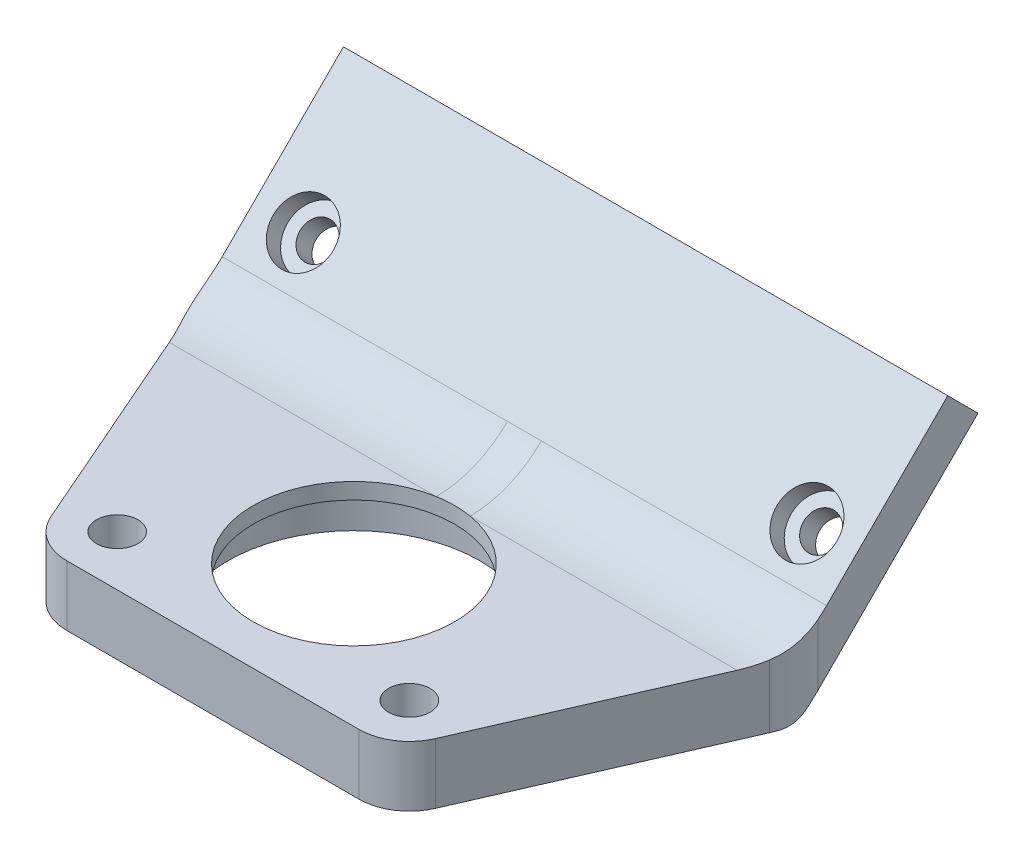
SolidWorks part; units mm, degrees
ref_plane "Alzado" through (0, 0, 0) normal (0, 0, 1) x (1, 0, 0)
ref_plane "Planta" through (0, 0, 0) normal (0, 1, 0) x (1, 0, 0)
ref_plane "Vista lateral" through (0, 0, 0) normal (1, 0, 0) x (0, 0, -1)
sketch "Croquis2" plane through (0, 0, 0) normal (1, 0, 0) x (0, 0, -1)
  line L0 (0, 0) -> (-28, 0)
  line L1 (-28, 0) -> (-28, 6)
  line L2 (-28, 6) -> (0, 6)
  line L3 (0, 6) -> (14.9605, 20.9605)
  line L4 (14.9605, 20.9605) -> (17.9605, 17.9605)
  line L5 (17.9605, 17.9605) -> (0, 0)
  dimension "D1" = 6
  dimension "D2" = 28
  dimension "D3" = 28
  dimension "D4" = 25.4
  dimension "D5" = 45
extrude "Saliente-Extruir1" add sketch "Croquis2" along normal blind 30 and the other way blind 30
ref_plane "Plano1" through (0, 0, 0) normal (0, -0.7071, -0.7071) x (-1, 0, 0)
sketch "Croquis3" plane through (0, 0, 0) normal (0, -0.7071, -0.7071) x (-1, 0, 0)
  line L0 (0, 0) -> (0, 25.4) construction
  line L1 (30, 25.4) -> (-30, 25.4) construction
  line L2 (-25, 12.7) -> (25, 12.7) construction
  circle A0 centre (-25, 12.7) radius 1.75
  circle A1 centre (25, 12.7) radius 1.75
  point P8 (0, 12.7)
  dimension "D2" = 3.5
  dimension "D1" = 50
extrude "Cortar-Extruir1" cut sketch "Croquis3" against normal up to surface (4.2426 mm away) up to face at (0, 13.4803, -7.4803)
ref_plane "Plano2" through (0, 3, 3) normal (0, 0.7071, 0.7071) x (1, 0, 0)
sketch "Croquis4" plane through (0, 3, 3) normal (0, 0.7071, 0.7071) x (1, 0, 0)
  circle A0 centre (-25, 12.7) radius 3
  circle A1 centre (25, 12.7) radius 3
  dimension "D1" = 6
extrude "Cortar-Extruir2" cut sketch "Croquis4" against normal blind 2
ref_plane "Plano3" through (0, 0, 0) normal (0, -1, 0) x (-1, 0, 0)
sketch "Croquis5" plane through (0, 0, 0) normal (0, -1, 0) x (-1, 0, 0)
  line L0 (14.5, -23) -> (-14.5, -23) construction
  line L1 (-30, 0) -> (-19.0821, -25.001)
  line L4 (-30, 0) -> (-30, -28)
  line L5 (-30, -28) -> (-14.5, -28)
  line L8 (0, 0) -> (0, -28) construction
  line L12 (30, -28) -> (-30, -28) construction
  line L13 (30, 0) -> (19.0821, -25.001)
  line L14 (30, 0) -> (30, -28)
  line L15 (30, -28) -> (14.5, -28)
  line L16 (0, -14) -> (0, -23) construction
  circle A0 centre (0, -14) radius 12.5
  circle A1 centre (0, -14) radius 12 construction
  circle A2 centre (0, -14) radius 10
  circle A3 centre (14.5, -23) radius 1.75
  circle A4 centre (-14.5, -23) radius 1.75
  arc A5 (-19.0821, -25.001) -> (-14.5, -28) centre (-14.5, -23) ccw
  arc A8 (19.0821, -25.001) -> (14.5, -28) centre (14.5, -23) cw
  circle A9 centre (-14.5, -23) radius 3 construction
  circle A10 centre (14.5, -23) radius 3 construction
  point P7 (0, -24)
  point P22 (0, -14)
  dimension "D1" = 24
  dimension "D2" = 20
  dimension "D3" = 25
  dimension "D4" = 3.5
  dimension "D7" = 6
  dimension "D5" = 29
  dimension "D6" = 9
extrude "Cortar-Extruir3" cut sketch "Croquis5" against normal up to surface (6 mm away) contours A2 | A3 | A4 | A5 L1 L4 L5 | L13 A8 L15 L14 region at (25.8314, 0, 18.7609) region at (-25.8314, 0, 18.7609) region at (0, 0, 14) region at (-14.5, 0, 23) region at (14.5, 0, 23) up to face at (0, 6, 14)
extrude "Cortar-Extruir4" cut sketch "Croquis5<4>" against normal blind 4.4 contours A0 A2 region at (12.1464, 0, 14)
sketch "Croquis5<4>" plane through (0, 0, 0) normal (0, -1, 0) x (-1, 0, 0) same geometry as "Croquis5"
fillet "Redondeo1" radius 10 1 edges at (0, 6, 0)
fillet "Redondeo2" radius 3 1 edges at (0, 0, 0)
fillet "Redondeo3" radius 10 2 edges at (-30, 3.5838, 0) (30, 3.5838, 0)
ref_plane "Plano4" through (0, 6, 0) normal (0, 1, 0) x (1, 0, 0)
sketch "Croquis6" plane through (0, 6, 0) normal (0, 1, 0) x (1, 0, 0)
  circle A0 centre (-14.5, -23) radius 2.06
  circle A1 centre (14.5, -23) radius 2.06
  dimension "D1" = 4.12
extrude "Cortar-Extruir5" cut sketch "Croquis6" against normal blind 4.2
